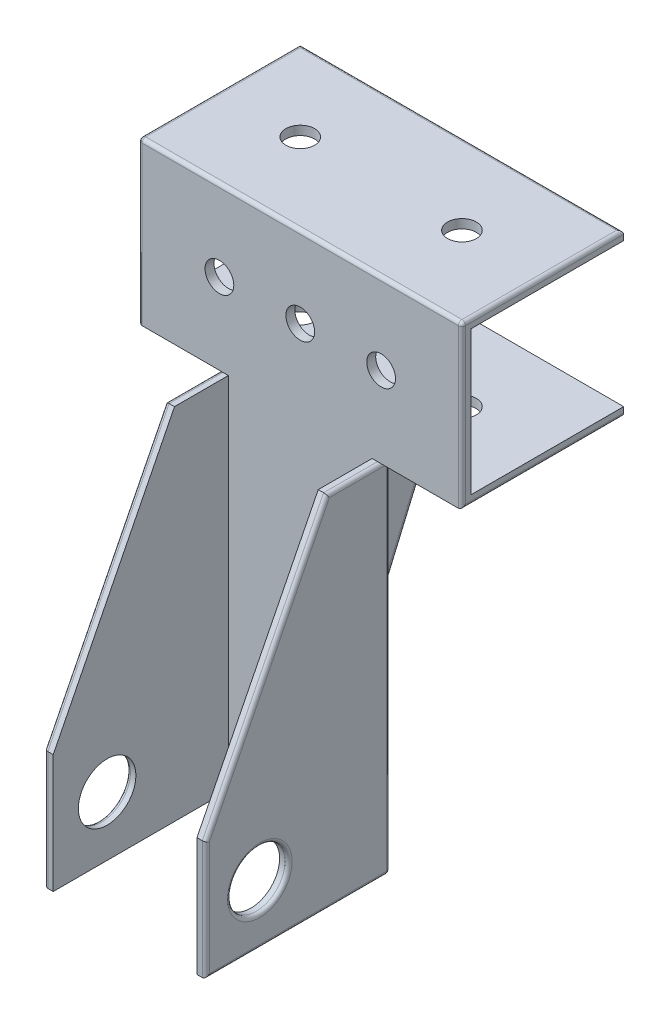
SolidWorks part; units mm, degrees
ref_plane "Płaszczyzna przednia" through (0, 0, 0) normal (0, 0, 1) x (1, 0, 0)
ref_plane "Płaszczyzna górna" through (0, 0, 0) normal (0, 1, 0) x (1, 0, 0)
ref_plane "Płaszczyzna prawa" through (0, 0, 0) normal (1, 0, 0) x (0, 0, -1)
sketch "Szkic1" plane through (0, 0, 0) normal (1, 0, 0) x (0, 0, -1)
  line L1 (-22.5, -22.5) -> (22.5, -22.5)
  line L2 (-22.5, -22.5) -> (-22.5, 22.5)
  line L3 (-22.5, 22.5) -> (22.5, 22.5)
  line L4 (22.5, -22.5) -> (22.5, 22.5)
  line L5 (-22.5, -22.5) -> (22.5, 22.5) construction
  line L6 (-22.5, 22.5) -> (22.5, -22.5) construction
  point P0 (0, 0)
  dimension "D1" = 45
  dimension "D2" = 45
extrude "Dodanie-wyciągnięcie1" add sketch "Szkic1" along normal blind 45 and the other way blind 45
sketch "Szkic2" plane through (-45, 0, 0) normal (-1, 0, 0) x (0, 0, 1)
  line L0 (-22.5, -22.5) -> (-22.5, 22.5) construction
  line L1 (-22.5, 20) -> (20, 20)
  line L2 (-22.5, 20) -> (-22.5, -20)
  line L3 (-22.5, -20) -> (20, -20)
  line L4 (20, 20) -> (20, -20)
  point P6 (-22.5, 0)
  dimension "D1" = 40
  dimension "D2" = 42.5
extrude "Wytnij-wyciągnięcie1" cut sketch "Szkic2" against normal through all and the other way through all
sketch "Szkic3" plane through (0, 0, 22.5) normal (0, 0, 1) x (1, 0, 0)
  line L0 (-45, -22.5) -> (45, -22.5) construction
  line L2 (-22.5, -22.5) -> (22.5, -22.5)
  line L3 (-22.5, -22.5) -> (-22.5, -122.5)
  line L4 (-22.5, -122.5) -> (22.5, -122.5)
  line L5 (22.5, -22.5) -> (22.5, -122.5)
  point P6 (0, -22.5)
  point P7 (0, -122.5)
  dimension "D1" = 45
  dimension "D2" = 100
extrude "Dodanie-wyciągnięcie2" add sketch "Szkic3" along normal blind 70 and the other way blind 2.5 separate body
sketch "Szkic4" plane through (0, -22.5, 0) normal (0, 1, 0) x (1, 0, 0)
  line L0 (22.5, -92.5) -> (-22.5, -92.5) construction
  line L1 (-20, -92.5) -> (20, -92.5)
  line L2 (-20, -92.5) -> (-20, -22.5)
  line L3 (-20, -22.5) -> (20, -22.5)
  line L4 (20, -92.5) -> (20, -22.5)
  line L5 (-22.5, -92.5) -> (-22.5, -20) construction
  line L6 (22.5, -92.5) -> (22.5, -20) construction
  line L7 (22.5, -20) -> (-22.5, -20) construction
  dimension "D1" = 2.5
  dimension "D3" = 2.5
  dimension "D4" = 2.5
extrude "Wytnij-wyciągnięcie2" cut sketch "Szkic4" against normal through all
sketch "Szkic5" plane through (-22.5, 0, 0) normal (-1, 0, 0) x (0, 0, 1)
  line L0 (-22.5, -20) -> (20, -20) construction
  line L1 (20, -22.5) -> (92.5, -22.5) construction
  line L3 (71.25, -122.5) -> (71.25, -89.5)
  line L6 (20, -122.5) -> (92.5, -122.5) construction
  line L7 (71.25, -89.5) -> (37.5, -22.5)
  line L8 (22.5, 22.5) -> (22.5, -22.5) construction
  circle A0 centre (56.25, -106) radius 8
  point P7 (56.25, -22.5)
  line M3 (20, -122.5) -> (92.5, -122.5)
  line M4 (92.5, -122.5) -> (92.5, -22.5)
  line M5 (92.5, -22.5) -> (20, -22.5)
  dimension "D1" = 16
  dimension "D2" = 86
  dimension "D3" = 15
  dimension "D4" = 33
  dimension "D5" = 15
extrude "Wytnij-wyciągnięcie4" cut sketch "Szkic5" against normal blind 90 contours L7 L3 M3 M4 M5 | A0 region at (-22.5, -62.8918, 74.2782) region at (-22.5, -106, 56.25)
fillet "Zaokrąglenie2" radius 1 8 edges at (-45, 22.5, 0) (0, 22.5, -22.5) (45, 22.5, 0) (0, 22.5, 22.5) (45, -22.5, 0) (-45, -22.5, 0) (-45, 0, 22.5) (45, 0, 22.5)
fillet "Zaokrąglenie3" radius 1 13 edges at (22.5, -72.5, 20) (22.5, -122.5, 45.625) (22.5, -106, 71.25) (22.5, -56, 54.375) (22.5, -22.5, 28.75) (22.5, -98, 56.25) (-22.5, -122.5, 45.625) (-22.5, -72.5, 20) (-22.5, -22.5, 28.75) (-22.5, -56, 54.375) (-22.5, -106, 71.25) (-22.5, -114, 56.25) (0, -122.5, 20)
sketch "Szkic6" plane through (0, 0, 22.5) normal (0, 0, 1) x (1, 0, 0)
  line L0 (-88.3668, 0) -> (83.7159, 0) construction
  line L1 (-45, -21.5) -> (-45, 21.5) construction
  line L2 (45, 21.5) -> (45, -21.5) construction
  circle A0 centre (-22.5, 0) radius 4
  circle A1 centre (0, 0) radius 4
  circle A2 centre (22.5, 0) radius 4
  dimension "D1" = 8
  dimension "D2" = 8
  dimension "D3" = 8
  dimension "D4" = 22.5
  dimension "D5" = 22.5
sketch "Szkic7" plane through (0, 22.5, 0) normal (0, 1, 0) x (1, 0, 0)
  line L0 (-69.8256, 0) -> (60.1678, 0) construction
  line L1 (45, 22.5) -> (45, -21.5) construction
  line L2 (-45, -21.5) -> (-45, 22.5) construction
  circle A0 centre (-22.5, 0) radius 4
  circle A1 centre (22.5, 0) radius 4
  dimension "D3" = 8
  dimension "D4" = 8
  dimension "D1" = 22.5
  dimension "D2" = 22.5
hole_wizard "Otwory ustalające Ø8.0mm1" positions "Szkic8" profile "Szkic9" hole size "Ø8.0" standard "ISO" end condition through all
sketch "Szkic8" plane through (0, 0, 22.5) normal (0, 0, 1) x (1, 0, 0)
  point P0 (-22.5, 0)
  point P3 (0, 0)
  point P6 (22.5, 0)
sketch "Szkic9" plane through (-22.5, 0, 22.5) normal (1, 0, 0) x (0, -1, 0)
  line L0 (0, 0) -> (0, 45)
  line L1 (0, 45) -> (4, 45)
  line L2 (4, 45) -> (4, 0)
  line L5 (4, 0) -> (0, 0)
  line L11 (0, -6.35) -> (0, 107.95) construction
  dimension "Średnica otworu na wylot" = 8
  dimension "Głębokość otworu na wylot" = 45
hole_wizard "Otwory ustalające Ø8.0mm3" positions "Szkic12" profile "Szkic13" hole size "Ø8.0" standard "ISO" end condition through all
sketch "Szkic12" plane through (0, 22.5, 0) normal (0, 1, 0) x (1, 0, 0)
  point P0 (22.5, 0)
  point P3 (-22.5, 0)
sketch "Szkic13" plane through (22.5, 22.5, 0) normal (1, 0, 0) x (0, 0, 1)
  line L0 (0, 0) -> (0, 145)
  line L1 (0, 145) -> (4, 145)
  line L2 (4, 145) -> (4, 0)
  line L5 (4, 0) -> (0, 0)
  line L11 (0, -6.35) -> (0, 107.95) construction
  dimension "Średnica otworu na wylot" = 8
  dimension "Głębokość otworu na wylot" = 145
ref_plane "Płaszczyzna1" through (0, 0, 0) normal (-1, 0, 0) x (0, 0, 1)
sketch "Szkic14" plane through (0, 0, 0) normal (-1, 0, 0) x (0, 0, 1)
  line L0 (20, -121.5) -> (-22.5, -22.5)
  line L1 (20, -121.5) -> (20, -22.5) construction
  line L2 (-22.5, -22.5) -> (20, -22.5)
  line L3 (20, -22.5) -> (20, -121.5)
  point P2 (0, 0)
  point P3 (0, 0)
extrude "Dodanie-wyciągnięcie3" add sketch "Szkic14" along normal blind 1.5 and the other way blind 1.5
fillet "Zaokrąglenie4" radius 1.5 2 edges at (1.5, -72, -1.25) (-1.5, -72, -1.25)
